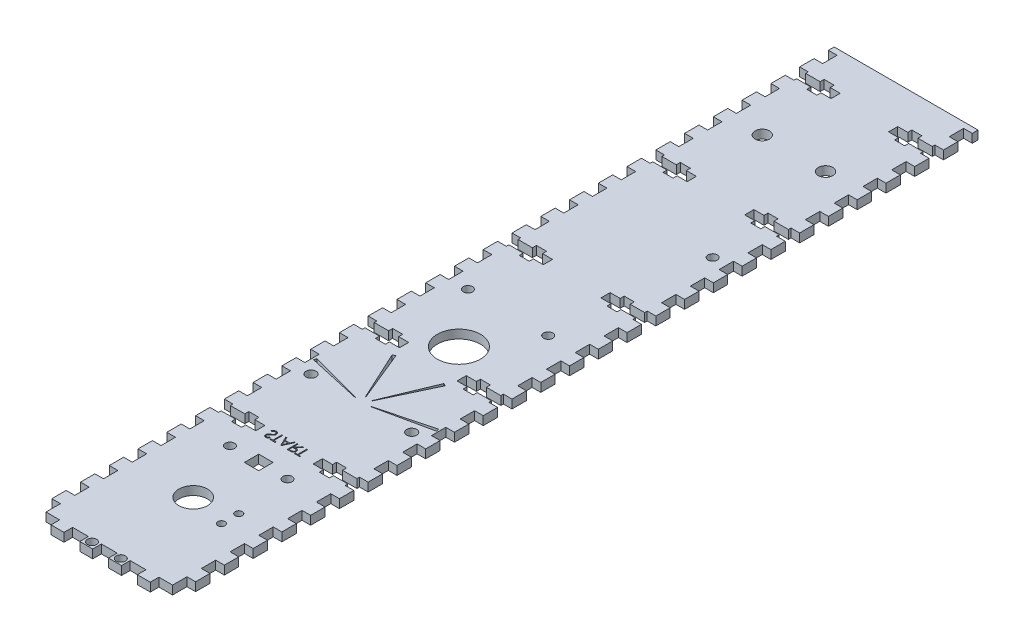
SolidWorks part; units mm, degrees
ref_plane "Plan de face" through (0, 0, 0) normal (0, 0, 1) x (1, 0, 0)
ref_plane "Plan de dessus" through (0, 0, 0) normal (0, 1, 0) x (1, 0, 0)
ref_plane "Plan de droite" through (0, 0, 0) normal (1, 0, 0) x (0, 0, -1)
sketch "Sketch1" plane through (0, 0, 0) normal (0, 0, 1) x (1, 0, 0)
  line L1 (-79.7436, 30.1282) -> (-29.7436, 30.1282)
  line L2 (-79.7436, 30.1282) -> (-79.7436, 27.1282)
  line L3 (-79.7436, 27.1282) -> (-29.7436, 27.1282)
  line L4 (-29.7436, 30.1282) -> (-29.7436, 27.1282)
  dimension "D1" = 50
  dimension "D2" = 3
extrude "Boss-Extrude1" add sketch "Sketch1" along normal blind 277
sketch "Sketch3" plane through (0, 30.1282, 0) normal (0, 1, 0) x (1, 0, 0)
  line L0 (-79.7436, -277) -> (-76.7436, -277)
  line L1 (-29.7436, -277) -> (-79.7436, -277) construction
  line L2 (-29.7436, 0) -> (-79.7436, 0) construction
  line L3 (-54.7436, 0) -> (-54.7436, -277) construction
  line L4 (-29.7436, -277) -> (-32.7436, -277)
  line L5 (-29.7436, -277) -> (-29.7436, -272)
  line L6 (-29.7436, -272) -> (-32.7436, -272)
  line L7 (-32.7436, -277) -> (-32.7436, -272)
  line L8 (-79.7436, -277) -> (-79.7436, -272)
  line L9 (-79.7436, -272) -> (-76.7436, -272)
  line L10 (-76.7436, -277) -> (-76.7436, -272)
  line L11 (-79.7436, -267) -> (-76.7436, -267)
  line L12 (-76.7436, -267) -> (-76.7436, -262)
  line L13 (-79.7436, -262) -> (-76.7436, -262)
  line L14 (-79.7436, -267) -> (-79.7436, -262)
  line L15 (-29.7436, -267) -> (-29.7436, -262)
  line L16 (-29.7436, -267) -> (-32.7436, -267)
  line L17 (-32.7436, -267) -> (-32.7436, -262)
  line L18 (-29.7436, -262) -> (-32.7436, -262)
  line L19 (-79.7436, -257) -> (-76.7436, -257)
  line L20 (-76.7436, -257) -> (-76.7436, -252)
  line L21 (-79.7436, -252) -> (-76.7436, -252)
  line L22 (-79.7436, -257) -> (-79.7436, -252)
  line L23 (-29.7436, -257) -> (-29.7436, -252)
  line L24 (-29.7436, -257) -> (-32.7436, -257)
  line L25 (-32.7436, -257) -> (-32.7436, -252)
  line L26 (-29.7436, -252) -> (-32.7436, -252)
  line L27 (-79.7436, -247) -> (-76.7436, -247)
  line L28 (-76.7436, -247) -> (-76.7436, -242)
  line L29 (-79.7436, -242) -> (-76.7436, -242)
  line L30 (-79.7436, -247) -> (-79.7436, -242)
  line L31 (-29.7436, -247) -> (-29.7436, -242)
  line L32 (-29.7436, -247) -> (-32.7436, -247)
  line L33 (-32.7436, -247) -> (-32.7436, -242)
  line L34 (-29.7436, -242) -> (-32.7436, -242)
  line L35 (-79.7436, -237) -> (-76.7436, -237)
  line L36 (-76.7436, -237) -> (-76.7436, -232)
  line L37 (-79.7436, -232) -> (-76.7436, -232)
  line L38 (-79.7436, -237) -> (-79.7436, -232)
  line L39 (-29.7436, -237) -> (-29.7436, -232)
  line L40 (-29.7436, -237) -> (-32.7436, -237)
  line L41 (-32.7436, -237) -> (-32.7436, -232)
  line L42 (-29.7436, -232) -> (-32.7436, -232)
  line L43 (-79.7436, -227) -> (-76.7436, -227)
  line L44 (-76.7436, -227) -> (-76.7436, -222)
  line L45 (-79.7436, -222) -> (-76.7436, -222)
  line L46 (-79.7436, -227) -> (-79.7436, -222)
  line L47 (-29.7436, -227) -> (-29.7436, -222)
  line L48 (-29.7436, -227) -> (-32.7436, -227)
  line L49 (-32.7436, -227) -> (-32.7436, -222)
  line L50 (-29.7436, -222) -> (-32.7436, -222)
  line L51 (-79.7436, -217) -> (-76.7436, -217)
  line L52 (-76.7436, -217) -> (-76.7436, -212)
  line L53 (-79.7436, -212) -> (-76.7436, -212)
  line L54 (-79.7436, -217) -> (-79.7436, -212)
  line L55 (-29.7436, -217) -> (-29.7436, -212)
  line L56 (-29.7436, -217) -> (-32.7436, -217)
  line L57 (-32.7436, -217) -> (-32.7436, -212)
  line L58 (-29.7436, -212) -> (-32.7436, -212)
  line L59 (-79.7436, -207) -> (-76.7436, -207)
  line L60 (-76.7436, -207) -> (-76.7436, -202)
  line L61 (-79.7436, -202) -> (-76.7436, -202)
  line L62 (-79.7436, -207) -> (-79.7436, -202)
  line L63 (-29.7436, -207) -> (-29.7436, -202)
  line L64 (-29.7436, -207) -> (-32.7436, -207)
  line L65 (-32.7436, -207) -> (-32.7436, -202)
  line L66 (-29.7436, -202) -> (-32.7436, -202)
  line L67 (-79.7436, -197) -> (-76.7436, -197)
  line L68 (-76.7436, -197) -> (-76.7436, -192)
  line L69 (-79.7436, -192) -> (-76.7436, -192)
  line L70 (-79.7436, -197) -> (-79.7436, -192)
  line L71 (-29.7436, -197) -> (-29.7436, -192)
  line L72 (-29.7436, -197) -> (-32.7436, -197)
  line L73 (-32.7436, -197) -> (-32.7436, -192)
  line L74 (-29.7436, -192) -> (-32.7436, -192)
  line L75 (-79.7436, -187) -> (-76.7436, -187)
  line L76 (-76.7436, -187) -> (-76.7436, -182)
  line L77 (-79.7436, -182) -> (-76.7436, -182)
  line L78 (-79.7436, -187) -> (-79.7436, -182)
  line L79 (-29.7436, -187) -> (-29.7436, -182)
  line L80 (-29.7436, -187) -> (-32.7436, -187)
  line L81 (-32.7436, -187) -> (-32.7436, -182)
  line L82 (-29.7436, -182) -> (-32.7436, -182)
  line L83 (-79.7436, -177) -> (-76.7436, -177)
  line L84 (-76.7436, -177) -> (-76.7436, -172)
  line L85 (-79.7436, -172) -> (-76.7436, -172)
  line L86 (-79.7436, -177) -> (-79.7436, -172)
  line L87 (-29.7436, -177) -> (-29.7436, -172)
  line L88 (-29.7436, -177) -> (-32.7436, -177)
  line L89 (-32.7436, -177) -> (-32.7436, -172)
  line L90 (-29.7436, -172) -> (-32.7436, -172)
  line L91 (-79.7436, -167) -> (-76.7436, -167)
  line L92 (-76.7436, -167) -> (-76.7436, -162)
  line L93 (-79.7436, -162) -> (-76.7436, -162)
  line L94 (-79.7436, -167) -> (-79.7436, -162)
  line L95 (-29.7436, -167) -> (-29.7436, -162)
  line L96 (-29.7436, -167) -> (-32.7436, -167)
  line L97 (-32.7436, -167) -> (-32.7436, -162)
  line L98 (-29.7436, -162) -> (-32.7436, -162)
  line L99 (-79.7436, -157) -> (-76.7436, -157)
  line L100 (-76.7436, -157) -> (-76.7436, -152)
  line L101 (-79.7436, -152) -> (-76.7436, -152)
  line L102 (-79.7436, -157) -> (-79.7436, -152)
  line L103 (-29.7436, -157) -> (-29.7436, -152)
  line L104 (-29.7436, -157) -> (-32.7436, -157)
  line L105 (-32.7436, -157) -> (-32.7436, -152)
  line L106 (-29.7436, -152) -> (-32.7436, -152)
  line L107 (-79.7436, -147) -> (-76.7436, -147)
  line L108 (-76.7436, -147) -> (-76.7436, -142)
  line L109 (-79.7436, -142) -> (-76.7436, -142)
  line L110 (-79.7436, -147) -> (-79.7436, -142)
  line L111 (-29.7436, -147) -> (-29.7436, -142)
  line L112 (-29.7436, -147) -> (-32.7436, -147)
  line L113 (-32.7436, -147) -> (-32.7436, -142)
  line L114 (-29.7436, -142) -> (-32.7436, -142)
  line L115 (-79.7436, -137) -> (-76.7436, -137)
  line L116 (-76.7436, -137) -> (-76.7436, -132)
  line L117 (-79.7436, -132) -> (-76.7436, -132)
  line L118 (-79.7436, -137) -> (-79.7436, -132)
  line L119 (-29.7436, -137) -> (-29.7436, -132)
  line L120 (-29.7436, -137) -> (-32.7436, -137)
  line L121 (-32.7436, -137) -> (-32.7436, -132)
  line L122 (-29.7436, -132) -> (-32.7436, -132)
  line L123 (-79.7436, -127) -> (-76.7436, -127)
  line L124 (-76.7436, -127) -> (-76.7436, -122)
  line L125 (-79.7436, -122) -> (-76.7436, -122)
  line L126 (-79.7436, -127) -> (-79.7436, -122)
  line L127 (-29.7436, -127) -> (-29.7436, -122)
  line L128 (-29.7436, -127) -> (-32.7436, -127)
  line L129 (-32.7436, -127) -> (-32.7436, -122)
  line L130 (-29.7436, -122) -> (-32.7436, -122)
  line L131 (-79.7436, -117) -> (-76.7436, -117)
  line L132 (-76.7436, -117) -> (-76.7436, -112)
  line L133 (-79.7436, -112) -> (-76.7436, -112)
  line L134 (-79.7436, -117) -> (-79.7436, -112)
  line L135 (-29.7436, -117) -> (-29.7436, -112)
  line L136 (-29.7436, -117) -> (-32.7436, -117)
  line L137 (-32.7436, -117) -> (-32.7436, -112)
  line L138 (-29.7436, -112) -> (-32.7436, -112)
  line L139 (-79.7436, -107) -> (-76.7436, -107)
  line L140 (-76.7436, -107) -> (-76.7436, -102)
  line L141 (-79.7436, -102) -> (-76.7436, -102)
  line L142 (-79.7436, -107) -> (-79.7436, -102)
  line L143 (-29.7436, -107) -> (-29.7436, -102)
  line L144 (-29.7436, -107) -> (-32.7436, -107)
  line L145 (-32.7436, -107) -> (-32.7436, -102)
  line L146 (-29.7436, -102) -> (-32.7436, -102)
  line L147 (-79.7436, -97) -> (-76.7436, -97)
  line L148 (-76.7436, -97) -> (-76.7436, -92)
  line L149 (-79.7436, -92) -> (-76.7436, -92)
  line L150 (-79.7436, -97) -> (-79.7436, -92)
  line L151 (-29.7436, -97) -> (-29.7436, -92)
  line L152 (-29.7436, -97) -> (-32.7436, -97)
  line L153 (-32.7436, -97) -> (-32.7436, -92)
  line L154 (-29.7436, -92) -> (-32.7436, -92)
  line L155 (-79.7436, -87) -> (-76.7436, -87)
  line L156 (-76.7436, -87) -> (-76.7436, -82)
  line L157 (-79.7436, -82) -> (-76.7436, -82)
  line L158 (-79.7436, -87) -> (-79.7436, -82)
  line L159 (-29.7436, -87) -> (-29.7436, -82)
  line L160 (-29.7436, -87) -> (-32.7436, -87)
  line L161 (-32.7436, -87) -> (-32.7436, -82)
  line L162 (-29.7436, -82) -> (-32.7436, -82)
  line L163 (-79.7436, -77) -> (-76.7436, -77)
  line L164 (-76.7436, -77) -> (-76.7436, -72)
  line L165 (-79.7436, -72) -> (-76.7436, -72)
  line L166 (-79.7436, -77) -> (-79.7436, -72)
  line L167 (-29.7436, -77) -> (-29.7436, -72)
  line L168 (-29.7436, -77) -> (-32.7436, -77)
  line L169 (-32.7436, -77) -> (-32.7436, -72)
  line L170 (-29.7436, -72) -> (-32.7436, -72)
  line L171 (-79.7436, -67) -> (-76.7436, -67)
  line L172 (-76.7436, -67) -> (-76.7436, -62)
  line L173 (-79.7436, -62) -> (-76.7436, -62)
  line L174 (-79.7436, -67) -> (-79.7436, -62)
  line L175 (-29.7436, -67) -> (-29.7436, -62)
  line L176 (-29.7436, -67) -> (-32.7436, -67)
  line L177 (-32.7436, -67) -> (-32.7436, -62)
  line L178 (-29.7436, -62) -> (-32.7436, -62)
  line L179 (-79.7436, -57) -> (-76.7436, -57)
  line L180 (-76.7436, -57) -> (-76.7436, -52)
  line L181 (-79.7436, -52) -> (-76.7436, -52)
  line L182 (-79.7436, -57) -> (-79.7436, -52)
  line L183 (-29.7436, -57) -> (-29.7436, -52)
  line L184 (-29.7436, -57) -> (-32.7436, -57)
  line L185 (-32.7436, -57) -> (-32.7436, -52)
  line L186 (-29.7436, -52) -> (-32.7436, -52)
  line L187 (-79.7436, -47) -> (-76.7436, -47)
  line L188 (-76.7436, -47) -> (-76.7436, -42)
  line L189 (-79.7436, -42) -> (-76.7436, -42)
  line L190 (-79.7436, -47) -> (-79.7436, -42)
  line L191 (-29.7436, -47) -> (-29.7436, -42)
  line L192 (-29.7436, -47) -> (-32.7436, -47)
  line L193 (-32.7436, -47) -> (-32.7436, -42)
  line L194 (-29.7436, -42) -> (-32.7436, -42)
  line L195 (-79.7436, -37) -> (-76.7436, -37)
  line L196 (-76.7436, -37) -> (-76.7436, -32)
  line L197 (-79.7436, -32) -> (-76.7436, -32)
  line L198 (-79.7436, -37) -> (-79.7436, -32)
  line L199 (-29.7436, -37) -> (-29.7436, -32)
  line L200 (-29.7436, -37) -> (-32.7436, -37)
  line L201 (-32.7436, -37) -> (-32.7436, -32)
  line L202 (-29.7436, -32) -> (-32.7436, -32)
  line L203 (-79.7436, -27) -> (-76.7436, -27)
  line L204 (-76.7436, -27) -> (-76.7436, -22)
  line L205 (-79.7436, -22) -> (-76.7436, -22)
  line L206 (-79.7436, -27) -> (-79.7436, -22)
  line L207 (-29.7436, -27) -> (-29.7436, -22)
  line L208 (-29.7436, -27) -> (-32.7436, -27)
  line L209 (-32.7436, -27) -> (-32.7436, -22)
  line L210 (-29.7436, -22) -> (-32.7436, -22)
  line L211 (-79.7436, -17) -> (-76.7436, -17)
  line L212 (-76.7436, -17) -> (-76.7436, -12)
  line L213 (-79.7436, -12) -> (-76.7436, -12)
  line L214 (-79.7436, -17) -> (-79.7436, -12)
  line L215 (-29.7436, -17) -> (-29.7436, -12)
  line L216 (-29.7436, -17) -> (-32.7436, -17)
  line L217 (-32.7436, -17) -> (-32.7436, -12)
  line L218 (-29.7436, -12) -> (-32.7436, -12)
  line L219 (-79.7436, -7) -> (-76.7436, -7)
  line L220 (-76.7436, -7) -> (-76.7436, -2)
  line L221 (-79.7436, -2) -> (-76.7436, -2)
  line L222 (-79.7436, -7) -> (-79.7436, -2)
  line L223 (-29.7436, -7) -> (-29.7436, -2)
  line L224 (-29.7436, -7) -> (-32.7436, -7)
  line L225 (-32.7436, -7) -> (-32.7436, -2)
  line L226 (-29.7436, -2) -> (-32.7436, -2)
  dimension "D1" = 3
  dimension "D2" = 5
  dimension "D3" = 28
extrude "Cut-Extrude1" cut sketch "Sketch3" against normal blind 3
sketch "Sketch6" plane through (0, 0, 277) normal (0, 0, 1) x (1, 0, 0)
  line L0 (-32.7436, 30.1282) -> (-76.7436, 30.1282) construction
  line L1 (-71.9936, 30.1282) -> (-67.4936, 30.1282)
  line L2 (-71.9936, 30.1282) -> (-71.9936, 27.1282)
  line L3 (-71.9936, 27.1282) -> (-67.4936, 27.1282)
  line L4 (-67.4936, 30.1282) -> (-67.4936, 27.1282)
  line L5 (-76.7436, 27.1282) -> (-32.7436, 27.1282) construction
  line L6 (-76.7436, 27.1282) -> (-76.7436, 30.1282) construction
  line L7 (-61.9936, 30.1282) -> (-61.9936, 27.1282)
  line L8 (-61.9936, 30.1282) -> (-57.4936, 30.1282)
  line L9 (-57.4936, 30.1282) -> (-57.4936, 27.1282)
  line L10 (-61.9936, 27.1282) -> (-57.4936, 27.1282)
  line L11 (-51.9936, 30.1282) -> (-51.9936, 27.1282)
  line L12 (-51.9936, 30.1282) -> (-47.4936, 30.1282)
  line L13 (-47.4936, 30.1282) -> (-47.4936, 27.1282)
  line L14 (-51.9936, 27.1282) -> (-47.4936, 27.1282)
  line L15 (-41.9936, 30.1282) -> (-41.9936, 27.1282)
  line L16 (-41.9936, 30.1282) -> (-37.4936, 30.1282)
  line L17 (-37.4936, 30.1282) -> (-37.4936, 27.1282)
  line L18 (-41.9936, 27.1282) -> (-37.4936, 27.1282)
  line L20 (-32.7436, 27.1282) -> (-32.7436, 30.1282) construction
  dimension "D1" = 4.75
  dimension "D2" = 4.5
  dimension "D4" = 4.75
  dimension "D3" = 4
extrude "Boss-Extrude2" add sketch "Sketch6" along normal blind 3
sketch "Sketch9" plane through (-32.7436, 0, 0) normal (1, 0, 0) x (0, 0, -1)
  line L0 (-267, 27.1282) -> (-262, 30.1282) construction
  line L1 (-262, 27.1282) -> (-267, 27.1282) construction
  line L2 (-262.9, 30.1282) -> (-266.1, 30.1282)
  line L3 (-262.9, 30.1282) -> (-262.9, 27.1282)
  line L4 (-262.9, 27.1282) -> (-266.1, 27.1282)
  line L5 (-266.1, 30.1282) -> (-266.1, 27.1282)
  line L6 (-262.9, 30.1282) -> (-266.1, 27.1282) construction
  line L7 (-262.9, 27.1282) -> (-266.1, 30.1282) construction
  line L8 (-212.9, 30.1282) -> (-212.9, 27.1282)
  line L9 (-212.9, 30.1282) -> (-216.1, 30.1282)
  line L10 (-216.1, 30.1282) -> (-216.1, 27.1282)
  line L11 (-212.9, 27.1282) -> (-216.1, 27.1282)
  line L12 (-162.9, 30.1282) -> (-162.9, 27.1282)
  line L13 (-162.9, 30.1282) -> (-166.1, 30.1282)
  line L14 (-166.1, 30.1282) -> (-166.1, 27.1282)
  line L15 (-162.9, 27.1282) -> (-166.1, 27.1282)
  line L16 (-112.9, 30.1282) -> (-112.9, 27.1282)
  line L17 (-112.9, 30.1282) -> (-116.1, 30.1282)
  line L18 (-116.1, 30.1282) -> (-116.1, 27.1282)
  line L19 (-112.9, 27.1282) -> (-116.1, 27.1282)
  line L20 (-62.9, 30.1282) -> (-62.9, 27.1282)
  line L21 (-62.9, 30.1282) -> (-66.1, 30.1282)
  line L22 (-66.1, 30.1282) -> (-66.1, 27.1282)
  line L23 (-62.9, 27.1282) -> (-66.1, 27.1282)
  line L24 (-12.9, 30.1282) -> (-12.9, 27.1282)
  line L25 (-12.9, 30.1282) -> (-16.1, 30.1282)
  line L26 (-16.1, 30.1282) -> (-16.1, 27.1282)
  line L27 (-12.9, 27.1282) -> (-16.1, 27.1282)
  point P4 (-264.5, 28.6282)
  dimension "D1" = 3.2
  dimension "D2" = 6
extrude "Cut-Extrude2" cut sketch "Sketch9" against normal blind 12
sketch "Sketch10" plane through (-76.7436, 0, 0) normal (-1, 0, 0) x (0, 0, 1)
  line L0 (267, 30.1282) -> (262, 27.1282) construction
  line L1 (267, 30.1282) -> (262, 30.1282) construction
  line L2 (262.9, 27.1282) -> (266.1, 27.1282)
  line L3 (262.9, 27.1282) -> (262.9, 30.1282)
  line L4 (262.9, 30.1282) -> (266.1, 30.1282)
  line L5 (266.1, 27.1282) -> (266.1, 30.1282)
  line L6 (262.9, 27.1282) -> (266.1, 30.1282) construction
  line L7 (262.9, 30.1282) -> (266.1, 27.1282) construction
  line L8 (212.9, 27.1282) -> (212.9, 30.1282)
  line L9 (212.9, 27.1282) -> (216.1, 27.1282)
  line L10 (216.1, 27.1282) -> (216.1, 30.1282)
  line L11 (212.9, 30.1282) -> (216.1, 30.1282)
  line L12 (162.9, 27.1282) -> (162.9, 30.1282)
  line L13 (162.9, 27.1282) -> (166.1, 27.1282)
  line L14 (166.1, 27.1282) -> (166.1, 30.1282)
  line L15 (162.9, 30.1282) -> (166.1, 30.1282)
  line L16 (112.9, 27.1282) -> (112.9, 30.1282)
  line L17 (112.9, 27.1282) -> (116.1, 27.1282)
  line L18 (116.1, 27.1282) -> (116.1, 30.1282)
  line L19 (112.9, 30.1282) -> (116.1, 30.1282)
  line L20 (62.9, 27.1282) -> (62.9, 30.1282)
  line L21 (62.9, 27.1282) -> (66.1, 27.1282)
  line L22 (66.1, 27.1282) -> (66.1, 30.1282)
  line L23 (62.9, 30.1282) -> (66.1, 30.1282)
  line L24 (12.9, 27.1282) -> (12.9, 30.1282)
  line L25 (12.9, 27.1282) -> (16.1, 27.1282)
  line L26 (16.1, 27.1282) -> (16.1, 30.1282)
  line L27 (12.9, 30.1282) -> (16.1, 30.1282)
  point P4 (264.5, 28.6282)
  dimension "D1" = 3.2
  dimension "D2" = 6
extrude "Cut-Extrude3" cut sketch "Sketch10" against normal blind 12
sketch "Sketch11" plane through (0, 27.1282, 0) normal (0, -1, 0) x (1, 0, 0)
  line L0 (-54.7436, 277) -> (-54.7436, 0) construction
  line L1 (-71.7436, 267.5) -> (-68.2436, 267.5)
  line L2 (-71.7436, 267.5) -> (-71.7436, 261.5)
  line L3 (-71.7436, 261.5) -> (-68.2436, 261.5)
  line L4 (-68.2436, 267.5) -> (-68.2436, 261.5)
  line L5 (-57.4936, 277) -> (-51.9936, 277) construction
  line L6 (-79.7436, 0) -> (-29.7436, 0) construction
  line L7 (-64.7436, 262.9) -> (-76.7436, 262.9) construction
  line L8 (-76.7436, 267) -> (-76.7436, 266.1) construction
  line L9 (-37.7436, 261.5) -> (-41.2436, 261.5)
  line L10 (-41.2436, 267.5) -> (-41.2436, 261.5)
  line L11 (-37.7436, 267.5) -> (-41.2436, 267.5)
  line L12 (-37.7436, 267.5) -> (-37.7436, 261.5)
  line L13 (-71.7436, 217.5) -> (-71.7436, 211.5)
  line L14 (-71.7436, 217.5) -> (-68.2436, 217.5)
  line L15 (-68.2436, 217.5) -> (-68.2436, 211.5)
  line L16 (-71.7436, 211.5) -> (-68.2436, 211.5)
  line L17 (-37.7436, 211.5) -> (-41.2436, 211.5)
  line L18 (-41.2436, 217.5) -> (-41.2436, 211.5)
  line L19 (-37.7436, 217.5) -> (-41.2436, 217.5)
  line L20 (-37.7436, 217.5) -> (-37.7436, 211.5)
  line L21 (-71.7436, 167.5) -> (-71.7436, 161.5)
  line L22 (-71.7436, 167.5) -> (-68.2436, 167.5)
  line L23 (-68.2436, 167.5) -> (-68.2436, 161.5)
  line L24 (-71.7436, 161.5) -> (-68.2436, 161.5)
  line L25 (-37.7436, 161.5) -> (-41.2436, 161.5)
  line L26 (-41.2436, 167.5) -> (-41.2436, 161.5)
  line L27 (-37.7436, 167.5) -> (-41.2436, 167.5)
  line L28 (-37.7436, 167.5) -> (-37.7436, 161.5)
  line L29 (-71.7436, 117.5) -> (-71.7436, 111.5)
  line L30 (-71.7436, 117.5) -> (-68.2436, 117.5)
  line L31 (-68.2436, 117.5) -> (-68.2436, 111.5)
  line L32 (-71.7436, 111.5) -> (-68.2436, 111.5)
  line L33 (-37.7436, 111.5) -> (-41.2436, 111.5)
  line L34 (-41.2436, 117.5) -> (-41.2436, 111.5)
  line L35 (-37.7436, 117.5) -> (-41.2436, 117.5)
  line L36 (-37.7436, 117.5) -> (-37.7436, 111.5)
  line L37 (-71.7436, 67.5) -> (-71.7436, 61.5)
  line L38 (-71.7436, 67.5) -> (-68.2436, 67.5)
  line L39 (-68.2436, 67.5) -> (-68.2436, 61.5)
  line L40 (-71.7436, 61.5) -> (-68.2436, 61.5)
  line L41 (-37.7436, 61.5) -> (-41.2436, 61.5)
  line L42 (-41.2436, 67.5) -> (-41.2436, 61.5)
  line L43 (-37.7436, 67.5) -> (-41.2436, 67.5)
  line L44 (-37.7436, 67.5) -> (-37.7436, 61.5)
  line L45 (-71.7436, 17.5) -> (-71.7436, 11.5)
  line L46 (-71.7436, 17.5) -> (-68.2436, 17.5)
  line L47 (-68.2436, 17.5) -> (-68.2436, 11.5)
  line L48 (-71.7436, 11.5) -> (-68.2436, 11.5)
  line L49 (-37.7436, 11.5) -> (-41.2436, 11.5)
  line L50 (-41.2436, 17.5) -> (-41.2436, 11.5)
  line L51 (-37.7436, 17.5) -> (-41.2436, 17.5)
  line L52 (-37.7436, 17.5) -> (-37.7436, 11.5)
  dimension "D1" = 6
  dimension "D2" = 1.4
  dimension "D3" = 5
  dimension "D4" = 3.5
  dimension "D5" = 6
extrude "Cut-Extrude4" cut sketch "Sketch11" against normal blind 12
sketch "Sketch12" plane through (0, 27.1282, 0) normal (0, -1, 0) x (1, 0, 0)
  line L0 (-51.9936, 280) -> (-47.4936, 280) construction
  line L1 (-61.9936, 280) -> (-57.4936, 280) construction
  circle A0 centre (-59.7436, 278) radius 1.6
  circle A1 centre (-49.7436, 278) radius 1.6
  dimension "D1" = 3.2
  dimension "D2" = 3.2
  dimension "D3" = 2
  dimension "D4" = 2
extrude "Cut-Extrude5" cut sketch "Sketch12" against normal blind 12
sketch "Sketch13" plane through (0, 27.1282, 0) normal (0, -1, 0) x (1, 0, 0)
  line L1 (-76.7436, 268.0925) -> (-63.236, 268.0925)
  line L2 (-76.7436, 268.0925) -> (-76.7436, 260.3098)
  line L3 (-76.7436, 260.3098) -> (-63.236, 260.3098)
  line L4 (-63.236, 268.0925) -> (-63.236, 260.3098)
  line L5 (-45.49, 268.9204) -> (-32.7436, 268.9204)
  line L6 (-45.49, 268.9204) -> (-45.49, 260.8754)
  line L7 (-45.49, 260.8754) -> (-32.7436, 260.8754)
  line L8 (-32.7436, 268.9204) -> (-32.7436, 260.8754)
  point P4 (-45.49, 268.9204)
  point P10 (-63.1206, 260.3098)
  point P11 (-63.236, 268.0925)
  point P12 (-45.3223, 260.8754)
  point P13 (0, 0)
extrude "Boss-Extrude3" add sketch "Sketch13" against normal blind 3
sketch "Sketch14" plane through (0, 27.1282, 0) normal (0, -1, 0) x (1, 0, 0)
  line L0 (-54.7436, 0) -> (-54.7436, 54.5316) construction
  line L1 (-79.7436, 0) -> (-29.7436, 0) construction
  circle A0 centre (-65.7436, 39) radius 2.5
  circle A1 centre (-43.7436, 39) radius 2.5
  point P10 (-54.7436, 0)
  dimension "D1" = 5
  dimension "D2" = 11
  dimension "D3" = 39
extrude "Cut-Extrude6" cut sketch "Sketch14" against normal through all
sketch "Sketch15" plane through (0, 27.1282, 0) normal (0, -1, 0) x (1, 0, 0)
  line L0 (-57.4936, 277) -> (-51.9936, 277) construction
  line L1 (-70.4509, 136.6028) -> (-42.5509, 136.6028) construction
  line L2 (-70.4509, 136.6028) -> (-70.4509, 84.5028) construction
  line L3 (-70.4509, 84.5028) -> (-42.5509, 84.5028) construction
  line L4 (-42.5509, 136.6028) -> (-42.5509, 84.5028) construction
  line L5 (-42.5509, 136.6028) -> (-37.5009, 136.6028) construction
  line L6 (-42.5509, 136.6028) -> (-42.5509, 84.5028) construction
  line L7 (-42.5509, 84.5028) -> (-37.5009, 84.5028) construction
  line L8 (-37.5009, 136.6028) -> (-37.5009, 84.5028) construction
  circle A0 centre (-70.4509, 136.6028) radius 1.6
  circle A1 centre (-42.5509, 136.6028) radius 1.6
  circle A2 centre (-37.5009, 84.5028) radius 1.6
  circle A3 centre (-54.7436, 155.4617) radius 7.5
  point P14 (-54.7436, 277)
  dimension "D3" = 3.2
  dimension "D4" = 3.2
  dimension "D6" = 3.2
  dimension "D7" = 15
  dimension "D1" = 27.9
  dimension "D2" = 52.1
  dimension "D5" = 5.05
extrude "Cut-Extrude7" cut sketch "Sketch15" against normal through all
sketch "Sketch16" plane through (0, 27.1282, 0) normal (0, -1, 0) x (1, 0, 0)
  line L0 (-32.7436, 252) -> (-32.7436, 257) construction
  line L1 (-42.7436, 250) -> (-42.7436, 244) construction
  line L3 (-57.4936, 277) -> (-51.9936, 277) construction
  circle A0 centre (-42.7436, 250) radius 1.25
  circle A1 centre (-42.7436, 244) radius 1.25
  circle A2 centre (-55.5663, 247) radius 5
  point P8 (-42.7436, 247)
  dimension "D1" = 2.5
  dimension "D2" = 2.5
  dimension "D5" = 10
  dimension "D3" = 6
  dimension "D4" = 10
  dimension "D6" = 30
extrude "Cut-Extrude8" cut sketch "Sketch16" against normal through all
sketch "Sketch17" plane through (0, 27.1282, 0) normal (0, -1, 0) x (1, 0, 0)
  line L0 (-64.6841, 225.1039) -> (-44.6841, 225.1039) construction
  line L2 (-57.1841, 232.6039) -> (-57.1841, 217.6039) construction
  line L3 (-57.1841, 227.6039) -> (-52.1841, 227.6039)
  line L4 (-57.1841, 227.6039) -> (-57.1841, 222.6039)
  line L5 (-57.1841, 222.6039) -> (-52.1841, 222.6039)
  line L6 (-52.1841, 227.6039) -> (-52.1841, 222.6039)
  circle A2 centre (-64.6841, 225.1039) radius 1.6
  circle A3 centre (-44.6841, 225.1039) radius 1.6
  text T0 "START"
  point P7 (-54.6841, 225.1039)
  point P15 (-57.1841, 225.1039)
  point P16 (-54.6841, 227.6039)
  point P17 (-57.1841, 225.1039)
  dimension "D1" = 3.2
  dimension "D2" = 15
  dimension "D3" = 3.2
  dimension "D4" = 20
  dimension "D5" = 5
  dimension "D6" = 5
extrude "Cut-Extrude9" cut sketch "Sketch17" against normal blind 10
sketch "Sketch18" plane through (0, 27.1282, 0) normal (0, -1, 0) x (1, 0, 0)
  line L0 (-72.1841, 189.4311) -> (-37.1841, 189.4311) construction
  line L1 (-57.1841, 222.6039) -> (-52.1841, 222.6039) construction
  line L2 (-54.6841, 189.4311) -> (-33.4846, 183.8256) construction
  line L3 (-54.6841, 189.4311) -> (-75.8462, 183.6858) construction
  line L4 (-54.6841, 189.4311) -> (-63.8857, 169.527) construction
  line L5 (-54.6841, 189.4311) -> (-45.3514, 169.5882) construction
  line L6 (125.2591, 485.958) -> (158.0404, 485.958) construction
  line L9 (-863.7024, 468.9667) -> (-829.7978, 468.9667) construction
  line L10 (-54.6841, 189.4311) -> (-63.8857, 169.527)
  line L11 (-63.8857, 169.527) -> (-62.9687, 169.1282)
  line L12 (-62.9687, 169.1282) -> (-54.6841, 189.4311)
  line L13 (-54.6841, 189.4311) -> (-45.3514, 169.5882)
  line L14 (-45.3514, 169.5882) -> (-46.2658, 169.1833)
  line L15 (-46.2658, 169.1833) -> (-54.6841, 189.4311)
  line L16 (-54.6841, 189.4311) -> (-33.4846, 183.8256)
  line L17 (-33.4846, 183.8256) -> (-33.229, 184.7924)
  line L18 (-33.229, 184.7924) -> (-54.6841, 189.4311)
  line L19 (-54.6841, 189.4311) -> (-75.8462, 183.6858)
  line L20 (-75.8462, 183.6858) -> (-76.1082, 184.6509)
  line L21 (-76.1082, 184.6509) -> (-54.6841, 189.4311)
  circle A0 centre (-72.1841, 189.4311) radius 1.75
  circle A1 centre (-37.1841, 189.4311) radius 1.75
  arc A2 (-75.8462, 183.6858) -> (-33.4846, 183.8256) centre (-54.6841, 189.4311) ccw construction
  arc A3 (-72.1841, 189.4311) -> (-37.1841, 189.4311) centre (-54.6841, 189.4311) cw construction
  circle A4 centre (-54.6841, 189.4311) radius 2.8572
  point P4 (-54.6841, 189.4311)
  point P7 (-54.6841, 222.6039)
  dimension "D1" = 3.5
  dimension "D2" = 3.5
  dimension "D3" = 35
  dimension "D4" = 50
  dimension "D5" = 50
  dimension "D6" = 150
  dimension "D7" = 1
  dimension "D8" = 1
  dimension "D9" = 1
  dimension "D10" = 1
extrude "Cut-Extrude10" cut sketch "Sketch18" against normal through all both and the other way through all contours A0 | A1 | A4 L21 L20 L19 | A4 L10 L11 L12 | A4 L15 L14 L13 | A4 L16 L17 L18 region at (-60.6004, 27.1282, 175.8274) region at (-48.6782, 27.1282, 175.8667) region at (-40.2525, 27.1282, 185.9651) region at (-69.0926, 27.1282, 185.8699) region at (-72.1841, 27.1282, 189.4311) region at (-37.1841, 27.1282, 189.4311)
equation "\"3.é\"=2.2"
